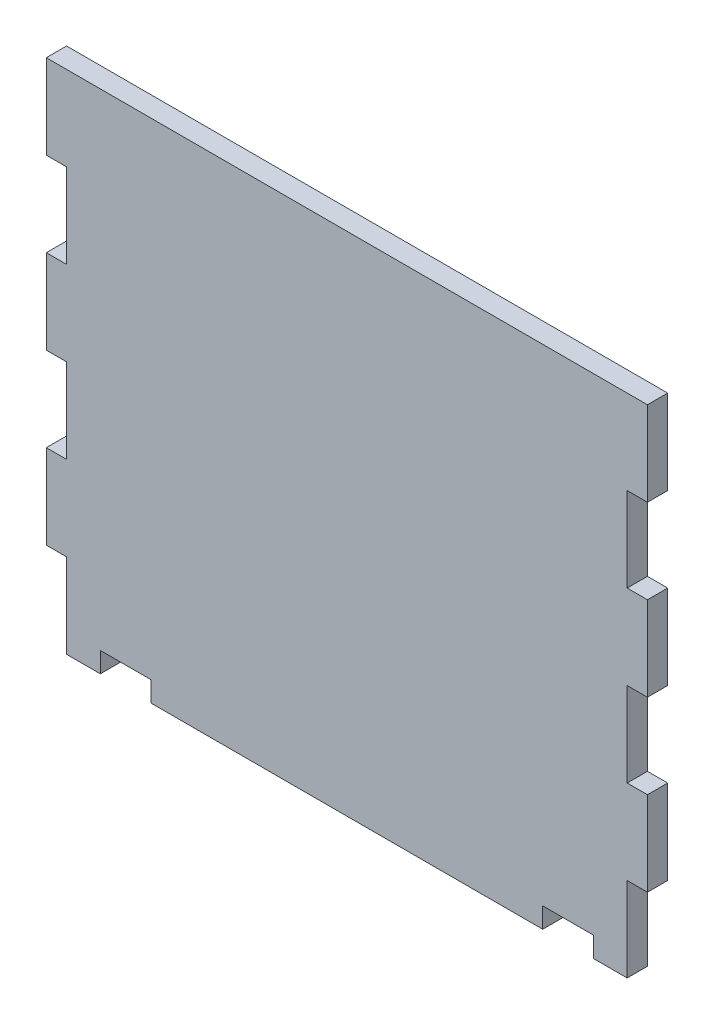
SolidWorks part; units mm, degrees
ref_plane "Front" through (0, 0, 0) normal (0, 0, 1) x (1, 0, 0)
ref_plane "Top" through (0, 0, 0) normal (0, 1, 0) x (1, 0, 0)
ref_plane "Right" through (0, 0, 0) normal (1, 0, 0) x (0, 0, -1)
sketch "Sketch1" plane through (0, 0, 0) normal (0, 0, 1) x (1, 0, 0)
  line L1 (0, 0) -> (-178, 0)
  line L2 (0, 0) -> (0, 150)
  line L3 (0, 150) -> (-178, 150)
  line L4 (-178, 0) -> (-178, 150)
  dimension "D1" = 150
  dimension "D2" = 178
extrude "Boss-Extrude1" add sketch "Sketch1" along normal blind 6
sketch "Sketch2" plane through (0, 0, 6) normal (0, 0, 1) x (1, 0, 0)
  line L0 (-178, 150) -> (-178, 0) construction
  line L1 (-178, 125) -> (-172, 125)
  line L2 (-178, 125) -> (-178, 100)
  line L3 (-178, 100) -> (-172, 100)
  line L4 (-172, 125) -> (-172, 100)
  line L5 (0, 150) -> (-178, 150) construction
  dimension "D1" = 25
  dimension "D2" = 25
  dimension "D3" = 6
extrude "Cut-Extrude1" cut sketch "Sketch2" against normal blind 6
pattern_linear "LPattern1" count 3 spacing 50 along (0, -1, 0) count 2 spacing 172 along (1, 0, 0) of "Cut-Extrude1"
sketch "Sketch3" plane through (0, 0, 6) normal (0, 0, 1) x (1, 0, 0)
  line L0 (-172, 0) -> (-6, 0) construction
  line L1 (-16, 0) -> (-31, 0)
  line L2 (-16, 0) -> (-16, 6)
  line L3 (-16, 6) -> (-31, 6)
  line L4 (-31, 0) -> (-31, 6)
  line L6 (-6, 25) -> (-6, 0) construction
  line L7 (-89, 150) -> (-89, 0) construction
  line L8 (0, 150) -> (-178, 150) construction
  line L9 (-147, 0) -> (-147, 6)
  line L10 (-162, 6) -> (-147, 6)
  line L11 (-162, 0) -> (-162, 6)
  line L12 (-162, 0) -> (-147, 0)
  dimension "D1" = 15
  dimension "D2" = 10
  dimension "D3" = 6
extrude "Cut-Extrude2" cut sketch "Sketch3" against normal through all
